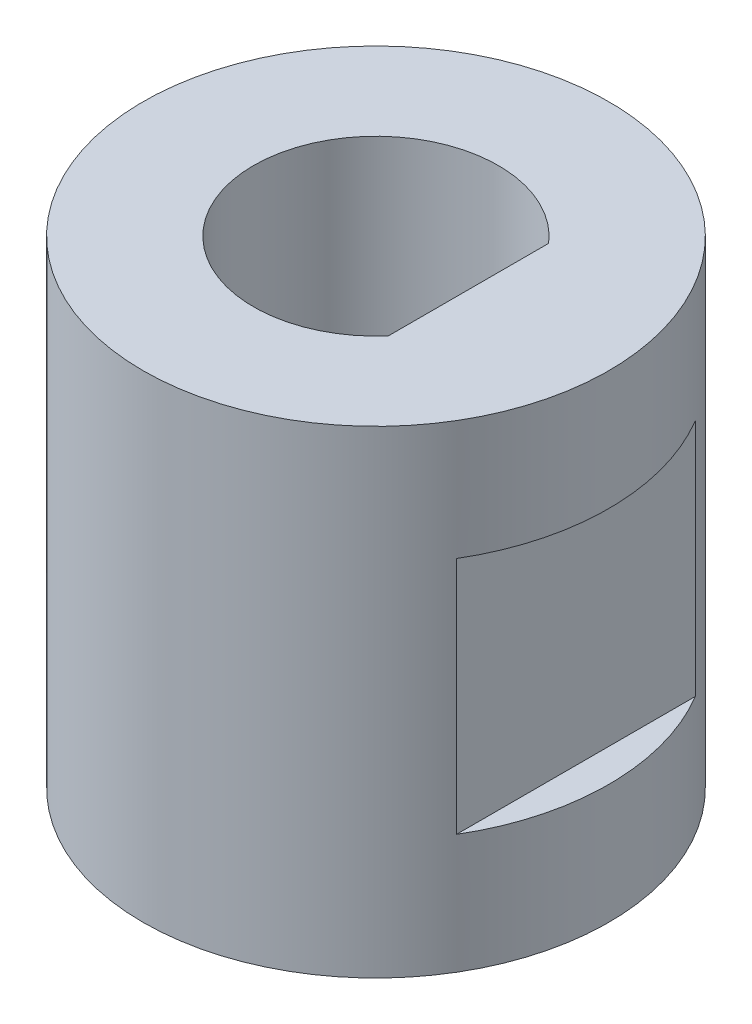
SolidWorks part; units mm, degrees
ref_plane "Front Plane" through (0, 0, 0) normal (0, 0, 1) x (1, 0, 0)
ref_plane "Top Plane" through (0, 0, 0) normal (0, 1, 0) x (1, 0, 0)
ref_plane "Right Plane" through (0, 0, 0) normal (1, 0, 0) x (0, 0, -1)
sketch "Sketch1" plane through (0, 0, 0) normal (0, 1, 0) x (1, 0, 0)
  circle A0 centre (0, 0) radius 3.9
  dimension "D1" = 7.8
extrude "Boss-Extrude1" add sketch "Sketch1" along normal blind 2 contours A0
sketch "Sketch3" plane through (0, 2, 0) normal (0, 1, 0) x (1, 0, 0)
  line L2 (-2, 3.3481) -> (2, 3.3481)
  line L3 (3.3481, 2) -> (3.3481, -2)
  arc A2 (-2, 3.3481) -> (3.3481, -2) centre (0, 0) ccw
  arc A3 (3.3481, 2) -> (2, 3.3481) centre (0, 0) ccw
  point P3 (3.3481, 2)
  point P4 (3.3481, -2)
  point P5 (2, 3.3481)
  point P6 (-2, 3.3481)
  dimension "D1" = 4
  dimension "D2" = 4
extrude "Boss-Extrude2" add sketch "Sketch3" along normal blind 4
sketch "Sketch4" plane through (0, 6, 0) normal (0, 1, 0) x (1, 0, 0)
  circle A0 centre (0, 0) radius 3.9
  dimension "D1" = 7.8
extrude "Boss-Extrude3" add sketch "Sketch4" along normal blind 2
sketch "Sketch5" plane through (0, 8, 0) normal (0, 1, 0) x (1, 0, 0)
  line L0 (-2.05, 0) -> (1.55, 0) construction
  line L1 (1.55, 1.3416) -> (1.55, -1.3416)
  arc A0 (1.55, 1.3416) -> (1.55, -1.3416) centre (0, 0) ccw
  dimension "D1" = 4.1
  dimension "D2" = 3.6
extrude "Cut-Extrude1" cut sketch "Sketch5" against normal through all
